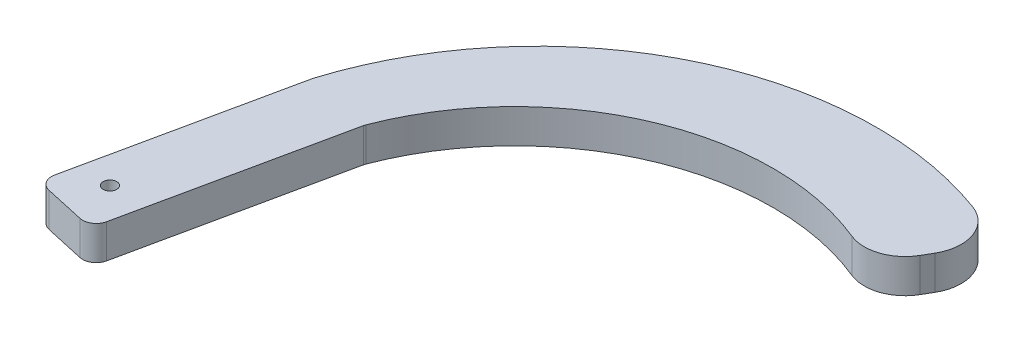
SolidWorks part; units mm, degrees
ref_plane "Front Plane" through (0, 0, 0) normal (0, 0, 1) x (1, 0, 0)
ref_plane "Top Plane" through (0, 0, 0) normal (0, 1, 0) x (1, 0, 0)
ref_plane "Right Plane" through (0, 0, 0) normal (1, 0, 0) x (0, 0, -1)
sketch "Sketch1" plane through (0, 0, 0) normal (0, 1, 0) x (1, 0, 0)
  line L4 (81.7789, 21.8904) -> (90.6254, 37.1304)
  line L5 (0, 0) -> (-9.0245, -42.228)
  line L7 (-9.0245, -42.228) -> (3.3728, -44.9865)
  line L8 (12.3973, -2.7585) -> (3.3728, -44.9865)
  arc A1 (12.3973, -2.7585) -> (81.7789, 21.8904) centre (57.5428, -19.8619) cw
  arc A2 (0, 0) -> (90.6254, 37.1304) centre (60.5579, -18.6443) cw
  circle A3 centre (-1.635, -36.3152) radius 1.27
  dimension "D2" = 12.7
  dimension "D3" = 15.24
extrude "Boss-Extrude1" add sketch "Sketch1" along normal blind 6.35
fillet "Fillet1" radius 7.62 2 edges at (90.6254, 3.175, -37.1304) (81.7789, 3.175, -21.8904)
fillet "Fillet2" radius 2.54 4 edges at (0, 3.175, 0) (-9.0245, 3.175, 42.228) (3.3728, 3.175, 44.9865) (12.3973, 3.175, 2.7585)
